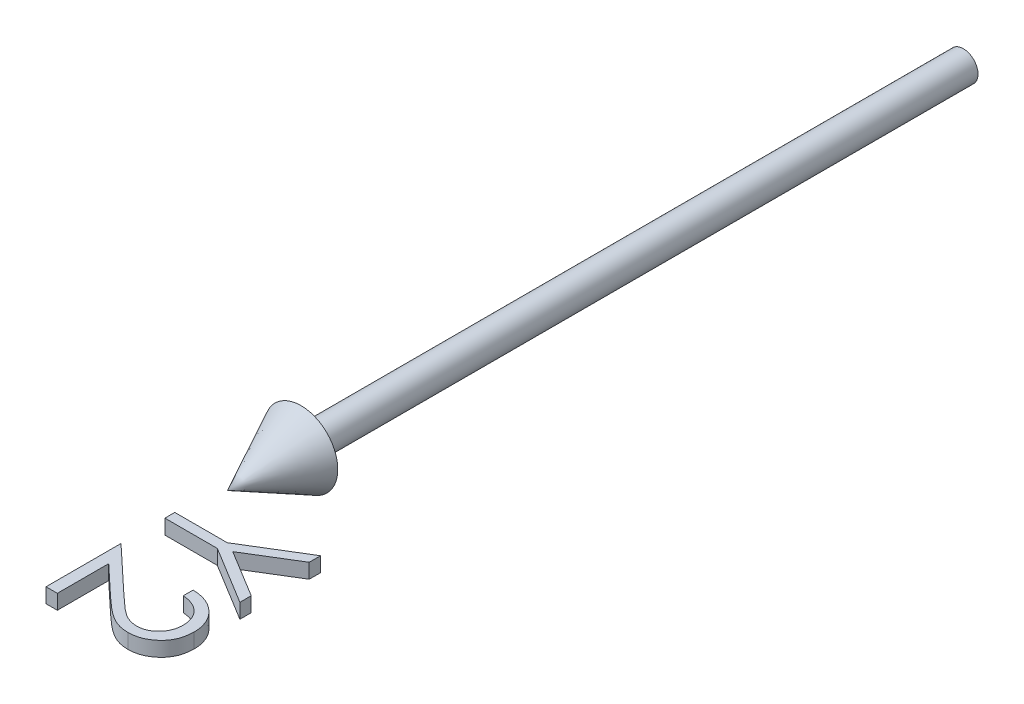
SolidWorks part; units mm, degrees
ref_plane "Front Plane" through (0, 0, 0) normal (0, 0, 1) x (1, 0, 0)
ref_plane "Top Plane" through (0, 0, 0) normal (0, 1, 0) x (1, 0, 0)
ref_plane "Right Plane" through (0, 0, 0) normal (1, 0, 0) x (0, 0, -1)
sketch "Sketch2" plane through (0, 0, 0) normal (0, 1, 0) x (1, 0, 0)
  line L0 (0, 41.95) -> (0, -114.4521) construction
  line L1 (-36.8894, 0) -> (41.4965, 0) construction
  line L2 (0, -100) -> (5, -90)
  line L3 (5, -90) -> (2, -90)
  line L4 (2, -90) -> (2, 0)
  line L5 (2, 0) -> (0, 0)
  line L6 (0, 0) -> (0, -100)
  dimension "D1" = 100
  dimension "D2" = 2
  dimension "D3" = 10
  dimension "D4" = 5
revolve "Revolve1" add sketch "Sketch2" angle 360 about L0
sketch "Sketch3" plane through (0, 0, 0) normal (0, 1, 0) x (1, 0, 0)
  line L0 (0, -101.5706) -> (0, -127.8138) construction
  text T0 "Y2\r\n" font "Century Gothic" height 15
extrude "Boss-Extrude1" add sketch "Sketch3" against normal blind 1 and the other way blind 1 separate body
equation "\"frame_arrow_length\"=100"
equation "\"D1@Sketch2\"=\"frame_arrow_length\""
equation "\"frame_arrow_odA\"=4"
equation "\"D2@Sketch2\"=\"frame_arrow_odA\"/2"
equation "\"frame_arrow_head_od\"=5"
equation "\"D4@Sketch2\"=\"frame_arrow_head_od\""
equation "\"frame_arrow_head_length\"=10"
equation "\"D3@Sketch2\"=\"frame_arrow_head_length\""
equation "\"tvarobot_theta1\"=30"
equation "\"link0_ringA_odA\"= 40"
equation "\"link0_ringA_odB\"= 25"
equation "\"link0_ringA_id\"= 20"
equation "\"link0_ringA_thickness\"= (\"link0_ringA_odB\" - \"link0_ringA_id\")/2"
equation "\"link0_ringA_height\"= 3"
equation "\"link0_ringA_heightA\"= 1.5"
equation "\"link0_ringA_heightB\"=\"link0_ringA_height\"-\"link0_ringA_heightA\""
equation "\"link0_ringB_odA\"= 40"
equation "\"link0_ringB_odB\"= 29"
equation "\"link0_ringB_id\"= \"link0_shaftA_bearing_id\"+1"
equation "\"link0_ringB_thickness\"= (\"link0_ringB_odB\" - \"link0_ringB_id\")/2"
equation "\"link0_ringB_height\"= 3"
equation "\"link0_ringB_heightA\"= 1.5"
equation "\"link0_ringB_heightB\"=\"link0_ringB_height\"-\"link0_ringB_heightA\""
equation "\"link0_shaftA_bearing_od\"=27"
equation "\"link0_shaftA_bearing_id\"=20"
equation "\"link0_shaftA_thrust_bearing_od\"=35"
equation "\"link0_shaftA_thrust_bearing_id\"=20.04"
equation "\"link0_shaftA_retaining_ring_id\"=18.5"
equation "\"link0_shaftA_retaining_ring_groove_width\"=1.5"
equation "\"link0_shaftA_spline_length\"=8.0"
equation "\"link0_shaftA_spline_depth\"=1.0"
equation "\"link0_shaftA_spline_width\"=4.0"
equation "\"link0_shaftA_odA\"=\"link0_shaftA_bearing_id\""
equation "\"link0_shaftA_odB\"=35"
equation "\"link0_shaftA_odC\"=\"link0_shaftA_bearing_id\""
equation "\"link0_shaftA_odD\"=\"link0_shaftA_odC\"-2*\"link0_shaftA_spline_depth\""
equation "\"link0_shaftA_odE\"=\"link0_shaftA_bearing_id\""
equation "\"link0_shaftA_odF\"=\"link0_shaftA_odE\"-2*\"link0_shaftA_spline_depth\""
equation "\"link0_shaftA_idA\"=10"
equation "\"link0_shaftA_idB\"=6"
equation "\"link0_shaftA_length\"=39.5"
equation "\"link0_shaftA_lengthA\"=8.0"
equation "\"link0_shaftA_lengthB\"=12.0"
equation "\"link0_shaftA_lengthC\"=35.0"
equation "\"link0_shaftA_lengthD\"=39.0"
equation "\"link0_shaftA_lengthE\"=\"link0_shaftA_length\"-\"link0_shaftA_lengthD\""
equation "\"link0_shaftA_offsetX\"=11"
equation "\"link0_shaftA_offsetY\"=0"
equation "\"link0_shaftA_bolt_pattern_dia\"=14"
equation "\"link0_motor_center_dist\"=26"
equation "\"link0_46t_pulley_spline_length\"=8"
equation "\"link0_46t_pulley_spline_depth\"=\"link0_shaftA_spline_depth\"*1.025"
equation "\"link0_46t_pulley_spline_width\"=\"link0_shaftA_spline_width\"*1.05"
equation "\"link0_46t_pulley_idA\"=\"link0_shaftA_bearing_id\"*1.025"
equation "\"link0_46t_pulley_idB\"=\"link0_46t_pulley_idA\"-2*\"link0_46t_pulley_spline_depth\""
equation "\"link0_shaftB_spline_length\"=10"
equation "\"link0_shaftB_spline_depth\"=1.0"
equation "\"link0_shaftB_spline_width\"=1.25"
equation "\"link0_shaftB_length\"=7"
equation "\"link0_shaftB_lengthA\"=1.5"
equation "\"link0_shaftB_lengthB\"=2.75"
equation "\"link0_shaftB_odA\"=32"
equation "\"link0_shaftB_odB\"=22"
equation "\"link0_shaftB_odC\"=20"
equation "\"link0_shaftB_idA\"=10"
equation "\"link0_shaftB_bolt_diameter\"=19"
equation "\"link0_shaftB_bearing_od\"=27"
equation "\"link0_shaftB_bearing_id\"=20"
equation "\"link0_motor_length\"=46.5"
equation "\"link0_motor_width\"=28.5"
equation "\"link0_motor_height\"=34"
equation "\"link0_motor_offset\"=8"
equation "\"link0_shellA_thickness\"=2.5"
equation "\"link0_shellB_thickness\"=\"link0_shellA_thickness\""
equation "\"link0_plateA_shellA_height\"=48"
equation "\"link0_shellA_width\" =\"link0_plateA_width\""
equation "\"link0_shellA_height\" = \"link0_plateA_shellA_height\"-\"link0_plateA_height\""
equation "\"link0_shellA_length\" = \"link0_plateA_lengthB\" "
equation "\"link0_shellB_length\"=\"link0_shellA_length\""
equation "\"link0_shellA_radius\" = 0.375*25.4"
equation "\"link0_shellA_radiusA\"= \"link0_plateA_radiusA\""
equation "\"link0_shellA_radiusB\"= \"link0_plateA_radiusB\""
equation "\"link0_shellA_radiusC\"= 3"
equation "\"link0_postA_height\"=7"
equation "\"link0_postA_width\"=16"
equation "\"link0_postA_length\"=20"
equation "\"link0_postA_posX\"=22"
equation "\"link0_postA_posY\"=17.5"
equation "\"link0_postA_pocket_width\"=6.0"
equation "\"link0_postA_pocket_length\"=2.5"
equation "\"link0_postA_pocket_depth\"=9"
equation "\"link0_postA_pocket_posZ\"=10"
equation "\"link0_postB_height\"=7"
equation "\"link0_postB_width\"=16"
equation "\"link0_postB_length\"=20"
equation "\"link0_postB_posX\"=22"
equation "\"link0_postB_posY\"=17.5"
equation "\"link0_postB_id\"=3.0"
equation "\"link0_postB_pocket_width\"=6.0"
equation "\"link0_postB_pocket_length\"=2.5"
equation "\"link0_postB_pocket_depth\"=9"
equation "\"link0_postB_pocket_posZ\"=10"
equation "\"link0_postC_height\"=7"
equation "\"link0_postC_width\"=16"
equation "\"link0_postC_length\"=20"
equation "\"link0_postC_posX\"=22"
equation "\"link0_postC_posY\"=17.5"
equation "\"link0_postC_id\"=3.0"
equation "\"link0_postC_pocket_width\"=6.0"
equation "\"link0_postC_pocket_length\"=2.5"
equation "\"link0_postC_pocket_depth\"=9"
equation "\"link0_postC_pocket_posZ\"=10"
equation "\"link0_postD_height\"=7"
equation "\"link0_postD_width\"=16"
equation "\"link0_postD_length\"=20"
equation "\"link0_postD_posX\"=22"
equation "\"link0_postD_posY\"=17.5"
equation "\"link0_postD_id\"=3.0"
equation "\"link0_postD_pocket_width\"=6.0"
equation "\"link0_postD_pocket_length\"=3.0"
equation "\"link0_postD_pocket_depth\"=9"
equation "\"link0_postD_pocket_posZ\"=10"
equation "\"link0_postE_height\"=5"
equation "\"link0_postE_width\"=16"
equation "\"link0_postE_length\"=\"link0_plateE_lengthA\"-\"link0_lip_height\""
equation "\"link0_postE_posZ\"=22"
equation "\"link0_postE_posX\"=17.5"
equation "\"link0_postE_posY\"=22"
equation "\"link0_postE_id\"=3.0"
equation "\"link0_postE_cbore_id\"=6.5"
equation "\"link0_postE_hole_id\"=3"
equation "\"link0_postF_posZ\"=22"
equation "\"link0_postF_posX\"=17.5"
equation "\"link0_postF_posY\"=\"link0_plateB_lengthA\"+4"
equation "\"link0_postF_id\"=3.0"
equation "\"link0_postF_cbore_id\"=6.5"
equation "\"link0_postF_hole_id\"=3"
equation "\"link0_postG_posZ\"=22"
equation "\"link0_postG_posX\"=17.5"
equation "\"link0_postG_posY\"=\"link0_plateB_lengthA\"+12"
equation "\"link0_postG_id\"=3.0"
equation "\"link0_postG_cbore_id\"=6.5"
equation "\"link0_postG_hole_id\"=3"
equation "\"link0_postHIJ_posY\"=6"
equation "\"link0_postH_posX\"=28"
equation "\"link0_postH_posY\"=20"
equation "\"link0_postH_posZ\"=20"
equation "\"link0_postH_length\"=10"
equation "\"link0_postI_posX\"=28"
equation "\"link0_postI_posY\"=20"
equation "\"link0_postI_posZ\"=135"
equation "\"link0_postI_length\"=10"
equation "\"link0_postJ_posX\"=28"
equation "\"link0_postJ_posY\"=20"
equation "\"link0_postJ_posZ\"=175"
equation "\"link0_postJ_length\"=10"
equation "\"link0_postK_posX\"=28"
equation "\"link0_postK_posY\"=20"
equation "\"link0_postK_posZ\"=175"
equation "\"link0_postK_length\"=10"
equation "\"link0_postL_posX\"=28"
equation "\"link0_postL_posY\"=20"
equation "\"link0_postL_posZ\"=135"
equation "\"link0_postL_length\"=10"
equation "\"link0_postM_posX\"=28"
equation "\"link0_postM_posY\"=20"
equation "\"link0_postM_posZ\"=35"
equation "\"link0_postM_length\"=10"
equation "\"link0_plateA_lengthA\"=30"
equation "\"link0_plateA_lengthB\"=150"
equation "\"link0_plateA_lengthC\"=30"
equation "\"link0_plateA_length\"=\"link0_plateA_lengthA\"+\"link0_plateA_lengthB\"+\"link0_plateA_lengthC\""
equation "\"link0_plateA_width\"=  68"
equation "\"link0_plateA_height\"= \"link0_plateA_radiusA\""
equation "\"link0_plateA_thickness\"=\"link0_shellA_thickness\""
equation "\"link0_plateA_radius\"= 9.5"
equation "\"link0_plateA_radiusA\"= 18"
equation "\"link0_plateA_radiusB\"= 18"
equation "\"link0_plateA_radiusC\"= 3"
equation "\"link0_plateB_length\"= 40"
equation "\"link0_plateB_width\"= \"link0_plateA_width\"*1.005"
equation "\"link0_plateB_height\"= \"link0_plateA_shellA_height\"*1.005"
equation "\"link0_plateB_lengthA\"=\"link0_lip_height\"+\"link0_plateD_thickness\"+\"link0_motor_mount_thickness\""
equation "\"link0_plateB_lengthB\"=\"link0_plateB_height\"-\"link0_plateB_lengthA\""
equation "\"link0_plateB_radiusA\"= \"link0_plateA_radiusA\""
equation "\"link0_plateB_radiusB\"= \"link0_plateA_radiusB\""
equation "\"link0_plateB_radiusC\"= 3"
equation "\"link0_plateB_idA\"=\"link0_shaftA_odC\"+1"
equation "\"link0_plateB_idB\"=\"link0_shaftA_bearing_od\"-2"
equation "\"link0_plateB_idC\"=\"link0_shaftA_bearing_od\"*1.005"
equation "\"link0_plateB_idD\"=\"link0_shaftA_thrust_bearing_od\"+1 "
equation "\"link0_plateB_depthA\"=1.0"
equation "\"link0_plateB_depthB\"=2.0"
equation "\"link0_plateB_depthC\"=8"
equation "\"link0_plateB_depthD\"=\"link0_plateB_length\"-\"link0_lip_height\"-\"link0_plateD_thickness\" "
equation "\"link0_plateC_length\"=\"link0_plateB_length\""
equation "\"link0_plateC_width\"= \"link0_plateB_width\""
equation "\"link0_plateC_height\"= .1*25.4"
equation "\"link0_plateA_hole_od\" = 0.1*25.4"
equation "\"link0_plateA_hole_delx\" = 0.5*25.4"
equation "\"link0_plateA_hole_delz\" = 0.75*25.4"
equation "\"link0_plateA_hole_offx\" = 0.0*25.4"
equation "\"link0_plateA_hole_offz\" = \"link0_plateA_length\"/2"
equation "\"link0_plateB_hole_od\" = 0.1*25.4"
equation "\"link0_plateB_hole_delx\"= 0.75*25.4"
equation "\"link0_plateB_hole_delz\"= 0.75*25.4"
equation "\"link0_plateB_hole_offx\"= 0.0*25.4"
equation "\"link0_plateB_hole_offz\"= 0.0*25.4"
equation "\"link0_plateC_hole_od\"= 0.1*25.4"
equation "\"link0_plateC_hole_delx\"= 0.75*25.4"
equation "\"link0_plateC_hole_delz\"= 0.75*25.4"
equation "\"link0_plateC_hole_offx\"= 0.0*25.4"
equation "\"link0_plateC_hole_offz\"= 0.0*25.4"
equation "\"link0_plateD_height\"=\"link0_plateB_height\"-2*\"link0_shellA_thickness\""
equation "\"link0_plateD_width\"=\"link0_plateB_width\"-2*\"link0_shellA_thickness\""
equation "\"link0_plateD_thickness\"=10"
equation "\"link0_plateD_radiusA\"=\"link0_plateB_radiusA\"-\"link0_shellA_thickness\""
equation "\"link0_plateD_odA\"= .375*25.4"
equation "\"link0_plateD_odB\"= .375*25.4"
equation "\"link0_plateD_bearing_id\"=20"
equation "\"link0_plateD_bearing_od\"=27"
equation "\"link0_plateE_radiusA\"=\"link0_plateA_radiusA\""
equation "\"link0_plateE_radiusB\"=\"link0_plateA_radiusB\""
equation "\"link0_plateE_radiusC\"=8.0"
equation "\"link0_plateE_length\"=30"
equation "\"link0_plateE_lengthA\"=16"
equation "\"link0_plateE_height\"=\"link0_plateB_height\""
equation "\"link0_plateE_width\"=\"link0_plateB_width\""
equation "\"link0_plateE_odA\"=\"gantry_coupler_id\"*0.99"
equation "\"link0_plateE_idA\"=\"link0_plateE_odA\"-20.0"
equation "\"link0_plateE_spline_depth\"=\"link0_poleA_spline_depth\"*1.05"
equation "\"link0_plateE_spline_width\"=\"link0_poleA_spline_width\"*1.075"
equation "\"link0_plateE_spline_length\"=\"link0_poleA_spline_length\""
equation "\"link0_plateE_coupler_length\"=46"
equation "\"link0_lip_height\"=5.0"
equation "\"link0_lip_thickness\"=2.0"
equation "\"link0_motor_mount_thickness\"=8.0"
equation "\"link0_motor_mount_idA\"=22"
equation "\"link0_motor_mount_idB\"=\"link0_shaftB_bearing_od\"*1.005"
equation "\"link0_motor_mount_idC\"=\"link0_shaftB_bearing_od\"-2"
equation "\"link0_motor_mount_depthA\"=5.5"
equation "\"link0_motor_mount_height\"=\"link0_plateD_height\""
equation "\"link0_motor_mount_width\"=\"link0_plateD_width\""
equation "\"link0_motor_mountL_height\"=36"
equation "\"link0_motor_mountL_heightA\"=12"
equation "\"link0_motor_mountL_length\"=50"
equation "\"link0_motor_mountL_lengthA\"=36"
equation "\"gantry_coupler_od\"=25.4*2.0"
equation "\"gantry_coupler_id\"=1.645*25.4"
equation "\"gantry_coupler_offsetX\"=\"link0_plateE_width\"/2"
equation "\"link0_poleA_odA\"=20"
equation "\"link0_poleA_odB\"=36"
equation "\"link0_poleA_idA\"=\"link0_poleA_odA\"-2*\"link0_poleA_thickness\""
equation "\"link0_poleA_idB\"=(\"link0_plateE_idA\"/2+1.5*\"link0_lip_thickness\")*1.04"
equation "\"link0_poleA_thickness\"=3.5"
equation "\"link0_poleA_length\"=100"
equation "\"link0_poleA_lengthA\"=18.5"
equation "\"link0_poleA_lengthB\"=80"
equation "\"link0_poleA_gasket_thickness\"=1.5"
equation "\"link0_poleA_spline_depth\"=1.0"
equation "\"link0_poleA_spline_width\"=4.0"
equation "\"link0_poleA_spline_length\"=10.0"
equation "\"link1_plateB_length\"=30"
equation "\"link1_lip_height\"=\"link0_lip_height\""
equation "\"link0_tension_plateA_width\"=12"
equation "\"link0_tension_plateA_lengthA\"=10.5"
equation "\"link0_tension_plateB_width\"=\"link0_tension_plateA_width\""
equation "\"link0_tension_plateB_lengthA\"=\"link0_tension_plateA_lengthA\""
equation "\"link0_tension_wheelA_posZ\"=7"
equation "\"link0_tension_wheelA_posX\"=\"link0_plateD_height\"/2-\"link0_tension_plateA_lengthA\""
equation "\"link0_m2_clear_hole_id\"=2.35"
equation "\"link0_m2_insert_hole_id\"=2.5"
equation "\"link0_m2_tap_hole_id\"=1.75"
equation "\"link0_m2_nut_socket_width\"=4.25"
equation "\"link0_m2_nut_socket_depth\"=2.5"
equation "\"link0_m2_cbore_id\"=3.75"
equation "\"link0_m2_cbore_depth\"=7"
equation "\"link0_m2_5_clear_hole_id\"=2.75"
equation "\"link0_m2_5_insert_hole_id\"=2.75"
equation "\"link0_m2_5_tap_hole_id\"=2.25"
equation "\"link0_m2_5_nut_socket_width\"=5.25"
equation "\"link0_m2_5_nut_socket_depth\"=2.5"
equation "\"link0_m2_5_cbore_id\"=4.75"
equation "\"link0_m2_5_cbore_depth\"=2.5"
equation "\"link0_m2_5_insert_access_length\"=6.0"
equation "\"link0_m2_5_insert_access_width\"=3.0"
equation "\"link0_m3_clear_hole_id\"=3.25"
equation "\"link0_m3_insert_hole_id\"=3"
equation "\"link0_m3_tap_hole_id\"=2.75"
equation "\"link0_m3_nut_socket_width\"=5.75"
equation "\"link0_m3_nut_socket_depth\"=4.0"
equation "\"link0_m3_cbore_id\"=5.75"
equation "\"link0_m3_cbore_depth\"=3.5"
equation "\"link0_m3_insert_access_length\"=4.5"
equation "\"link0_m3_insert_access_width\"=3.5"
equation "\"link0_rpi_mount_height\"=6"
equation "\"link0_rpi_mount_width\"=49"
equation "\"link0_rpi_mount_length\"=58"
equation "\"link0_rpi_mount_post_od\"=6"
equation "\"link0_rpi_mount_posZ\"=72"
equation "\"link0_rpi_mount_posX\"=11.5"
equation "\"link0_mcu_mount_height\"=5"
equation "\"link0_mcu_mount_width\"=49"
equation "\"link0_mcu_mount_length\"=58"
equation "\"link0_mcu_mount_post_od\"=6"
equation "\"link0_mcu_mount_posZ\"=164"
equation "\"link0_mcu_mount_posX\"=4"
equation "\"link0_pwr_mount_height\"=4"
equation "\"link0_pwr_mount_width\"=15.75"
equation "\"link0_pwr_mount_length\"=75.75"
equation "\"link0_pwr_mount_post_od\"=6"
equation "\"link0_pwr_mount_posZ\"=75"
equation "\"link0_pwr_mount_posX\"=16"
equation "\"link0_pwr_board_height\"=6"
equation "\"link0_pwr_board_width\"=21"
equation "\"link0_pwr_board_length\"=80"
